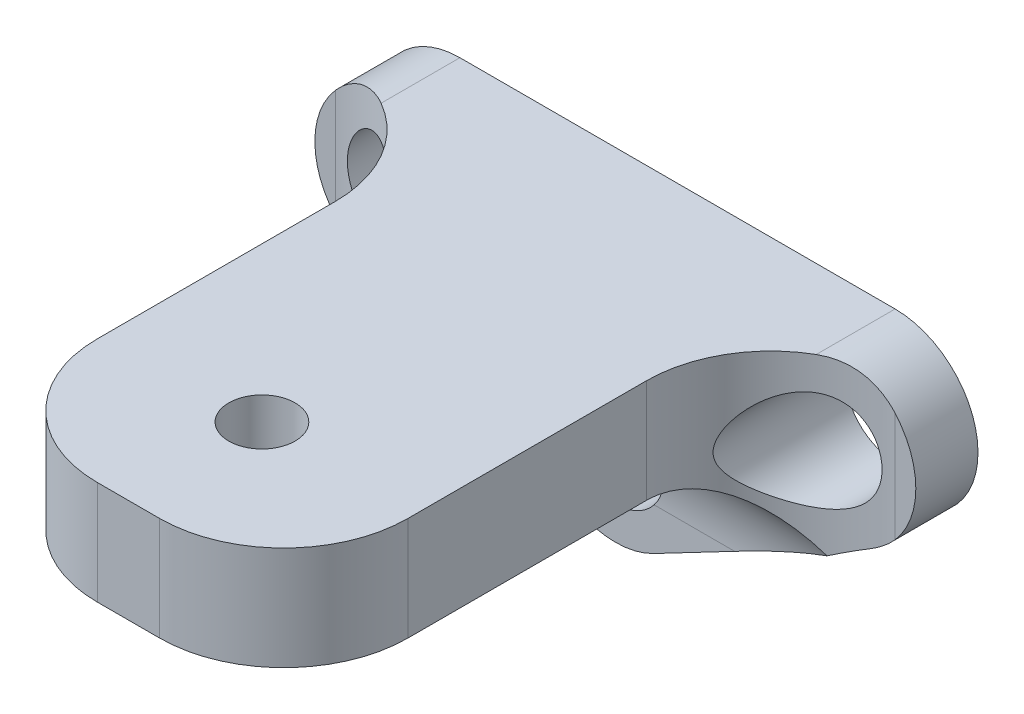
SolidWorks part; units mm, degrees
ref_plane "Piano frontale" through (0, 0, 0) normal (0, 0, 1) x (1, 0, 0)
ref_plane "Piano superiore" through (0, 0, 0) normal (0, 1, 0) x (1, 0, 0)
ref_plane "Piano destro" through (0, 0, 0) normal (1, 0, 0) x (0, 0, -1)
sketch "Schizzo1" plane through (0, 0, 0) normal (0, 0, 1) x (1, 0, 0)
  line L0 (0, 0) -> (21, 0) construction
  line L1 (0, 4) -> (21, 4)
  line L4 (12.356, -9.0433) -> (22.856, -3.5433)
  line L5 (8.644, -9.0433) -> (-1.856, -3.5433)
  circle A0 centre (0, 0) radius 2.4
  circle A1 centre (21, 0) radius 2.4
  circle A2 centre (10.5, -5.5) radius 2.4
  arc A6 (0, 4) -> (-1.856, -3.5433) centre (0, 0) ccw
  arc A7 (22.856, -3.5433) -> (21, 4) centre (21, 0) ccw
  arc A8 (8.644, -9.0433) -> (12.356, -9.0433) centre (10.5, -5.5) ccw
  point P8 (10.5, 0)
  dimension "D1" = 4.8
  dimension "D2" = 21
  dimension "D3" = 5.5
  dimension "D4" = 4
extrude "Estrusione-Estrusione1" add sketch "Schizzo1" along normal blind 3
sketch "Schizzo2" plane through (0, 0, 3) normal (0, 0, 1) x (1, 0, 0)
  line L0 (0, 0) -> (21, 0) construction
  line L1 (21, 4) -> (0, 4) construction
  line L2 (3, -1) -> (18, -1)
  line L3 (3, -1) -> (3, 4)
  line L4 (3, 4) -> (18, 4)
  line L5 (18, -1) -> (18, 4)
  line L6 (3, -1) -> (18, 4) construction
  line L7 (3, 4) -> (18, -1) construction
  point P4 (10.5, 1.5)
  point P13 (10.5, 0)
  dimension "D1" = 15
  dimension "D2" = 5
extrude "Estrusione-Estrusione2" add sketch "Schizzo2" along normal offset from surface (32 mm away) 35 up to face at (10.5, -2.6959, 0)
sketch "Schizzo3" plane through (0, 4, 0) normal (0, 1, 0) x (1, 0, 0)
  line L1 (18, -26.5) -> (3, -26.5)
  line L2 (18, -35) -> (3, -35)
  line L4 (3, -35) -> (3, -3) construction
  line L8 (18, -35) -> (18, -26.5)
  line L9 (18, -35) -> (18, -3) construction
  line L10 (3, -26.5) -> (3, -35)
  circle A0 centre (10.4464, -20) radius 1.6
  point P2 (0, 0)
  point P3 (10.4539, -20.0271)
  point P5 (10.4464, -20)
  dimension "D1" = 3.2
  dimension "D2" = 8.5
extrude "Taglio-Estrusione1" cut sketch "Schizzo3" against normal through all
fillet "Raccordo1" radius 6 2 edges at (18, 1.5, 26.5) (3, 1.5, 26.5)
chamfer "Smusso1" distance 2 angle 45 1 edges at (10.4464, -1, 21.6)
fillet "Raccordo2" radius 6 3 edges at (18, 1.5, 3) (3, 1.5, 3) (10.5, -1, 3)
